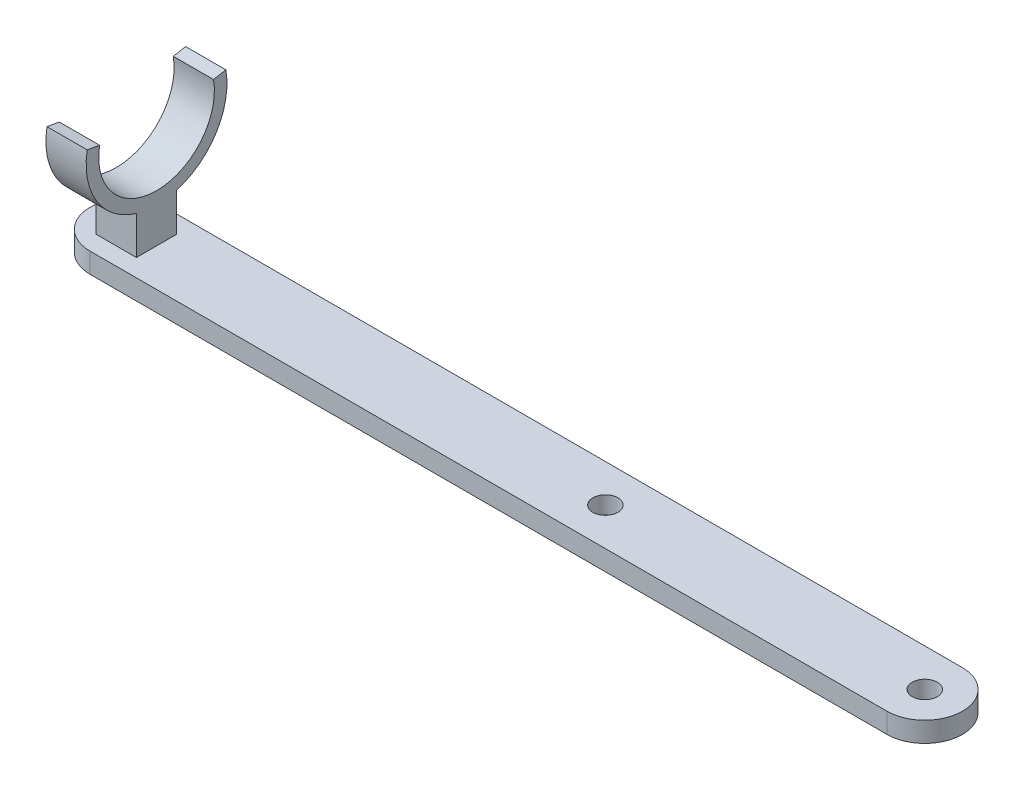
SolidWorks part; units mm, degrees
ref_plane "Front Plane" through (0, 0, 0) normal (0, 0, 1) x (1, 0, 0)
ref_plane "Top Plane" through (0, 0, 0) normal (0, 1, 0) x (1, 0, 0)
ref_plane "Right Plane" through (0, 0, 0) normal (1, 0, 0) x (0, 0, -1)
ref_axis "X Axis" through (-39.3295, 0, 0) along (1, 0, 0)
ref_axis "Y Axis" through (0, 0, -37.7472) along (0, 0, 1)
ref_axis "Z Axis" through (0, 35.6627, 0) along (0, -1, 0)
sketch "Sketch2" plane through (0, 0, 0) normal (0, 1, 0) x (1, 0, 0)
  line L0 (-31.75, 0) -> (31.75, 0) construction
  line L1 (-30, 0) -> (30, 0) construction
  line L4 (-31.75, 0) -> (-126.75, 0) construction
  line L5 (-126.75, 0) -> (31.75, 0) construction
  line L6 (-126.75, 7.5) -> (31.75, 7.5)
  line L7 (-126.75, -7.5) -> (31.75, -7.5)
  circle A0 centre (-31.75, 0) radius 2.5
  circle A1 centre (31.75, 0) radius 2.5
  arc A4 (-126.75, 7.5) -> (-126.75, -7.5) centre (-126.75, 0) ccw
  arc A5 (31.75, -7.5) -> (31.75, 7.5) centre (31.75, 0) ccw
  point P2 (0, 0)
  point P8 (0, 0)
  point P9 (-47.5, 0)
  dimension "D2" = 5
  dimension "D4" = 15
  dimension "D1" = 63.5
  dimension "D3" = 95
extrude "Boss-Extrude1" add sketch "Sketch2" along normal blind 4
ref_plane "Plane1" through (-125, 0, 0) normal (1, 0, 0) x (0, 0, -1)
sketch "Sketch3" plane through (-125, 0, 0) normal (1, 0, 0) x (0, 0, -1)
  line L0 (0, 0) -> (0, 25) construction
  line L1 (-13.7873, 27.4311) -> (-11.3253, 26.997)
  line L3 (11.3253, 26.997) -> (13.7873, 27.4311)
  arc A0 (11.3253, 26.997) -> (-11.3253, 26.997) centre (0, 25) cw
  arc A1 (13.7873, 27.4311) -> (-13.7873, 27.4311) centre (0, 25) cw
  dimension "D2" = 11.5
  dimension "D3" = 2.5
  dimension "D1" = 25
extrude "Boss-Extrude2" add sketch "Sketch3" along normal blind 4 and the other way blind 4 separate body
sketch "Sketch4" plane through (0, 4, 0) normal (0, 1, 0) x (1, 0, 0)
  line L1 (-129, -4) -> (-121, -4)
  line L2 (-129, -4) -> (-129, 4)
  line L3 (-129, 4) -> (-121, 4)
  line L4 (-121, -4) -> (-121, 4)
  line L6 (-31.75, 0) -> (-121, 0) construction
  line L7 (-129, 11.5) -> (-129, -11.5) construction
  line L8 (-121, -11.5) -> (-121, 11.5) construction
  point P4 (0, 0)
  point P7 (0, 0)
  point P11 (-121.285, 5.715)
  dimension "D1" = 8
extrude "Boss-Extrude3" add sketch "Sketch4" along normal up to surface (7.5836 mm away) up to face at (-125, 19.2155, 0)
sketch "Sketch5" plane through (0, 0, 0) normal (0, -1, 0) x (1, 0, 0)
  circle A0 centre (-31.75, 0) radius 5.4
  circle A1 centre (31.75, 0) radius 5.4
  dimension "D1" = 10.8
extrude "Cut-Extrude1" cut sketch "Sketch5" against normal blind 0.5
